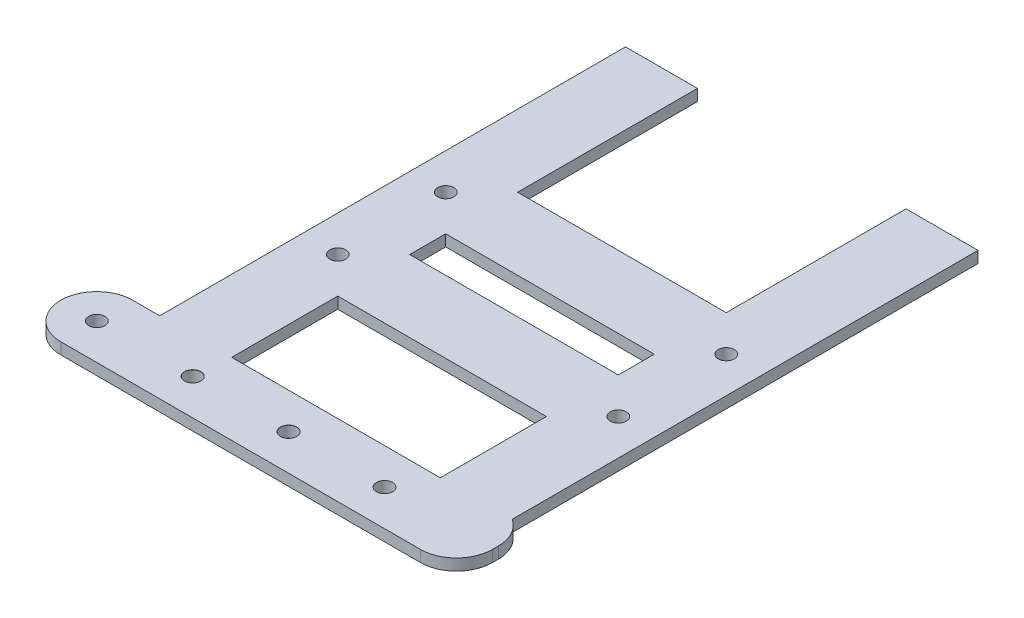
SolidWorks part; units mm, degrees
ref_plane "Front Plane" through (0, 0, 0) normal (0, 0, 1) x (1, 0, 0)
ref_plane "Top Plane" through (0, 0, 0) normal (0, 1, 0) x (1, 0, 0)
ref_plane "Right Plane" through (0, 0, 0) normal (1, 0, 0) x (0, 0, -1)
sketch "Sketch1" plane through (0, 0, 0) normal (0, 1, 0) x (1, 0, 0)
  line L1 (-50, -200) -> (50, -200)
  line L2 (-50, -200) -> (-50, 200)
  line L3 (-50, 200) -> (50, 200)
  line L4 (50, -200) -> (50, 200)
  line L5 (-50, -200) -> (50, 200) construction
  line L6 (-50, 200) -> (50, -200) construction
  point P0 (0, 0)
  dimension "D1" = 100
  dimension "D2" = 400
extrude "Boss-Extrude1" add sketch "Sketch1" along normal blind 3.175
sketch "Sketch2" plane through (0, 3.175, 0) normal (0, 1, 0) x (1, 0, 0)
  line L0 (50, 200) -> (-50, 200) construction
  line L1 (-40, 200) -> (-40, -200) construction
  line L2 (-50, -200) -> (50, -200) construction
  line L3 (-50, 95) -> (50, 95) construction
  line L4 (40, 200) -> (40, -200) construction
  line L5 (0, -200) -> (0, 200) construction
  line L6 (50, -200) -> (50, 200) construction
  line L7 (-50, 190) -> (50, 190) construction
  line L8 (-50, 200) -> (-50, -200) construction
  line L9 (-50, -190) -> (50, -190) construction
  dimension "D1" = 80
  dimension "D2" = 40
  dimension "D4" = 10
  dimension "D5" = 10
  dimension "D3" = 380
  dimension "D6" = 295
hole_wizard "M4 Clearance Hole2" positions "Sketch3" profile "Sketch5" hole size "M4" standard "AS" end condition up to next
sketch "Sketch3" plane through (0, 3.175, 0) normal (0, 1, 0) x (1, 0, 0)
  line L0 (-40, 200) -> (-40, -200) construction
  line L1 (-50, 190) -> (50, 190) construction
  line L2 (40, 200) -> (40, -200) construction
  line L3 (-50, -190) -> (50, -190) construction
  line L4 (-50, 95) -> (50, 95) construction
  point P0 (-40, 190)
  point P6 (40, 190)
  point P10 (40, -190)
  point P12 (-40, -190)
  point P17 (-40, 95)
  point P21 (40, 95)
sketch "Sketch5" plane through (-40, 3.175, -190) normal (1, 0, 0) x (0, 0, 1)
  line L0 (0, 0) -> (0, 3.175)
  line L1 (0, 3.175) -> (2.25, 3.175)
  line L2 (2.25, 3.175) -> (2.25, 0)
  line L5 (2.25, 0) -> (0, 0)
  line L11 (0, -6.35) -> (0, 107.95) construction
  dimension "Thru Hole Dia." = 4.5
  dimension "Thru Hole Depth" = 3.175
sketch "Sketch7" plane through (50, 0, 0) normal (1, 0, 0) x (0, 0, -1)
  line L1 (-200, 0) -> (200, 0)
  line L2 (-200, 0) -> (-200, 3.175)
  line L3 (-200, 3.175) -> (200, 3.175)
  line L4 (200, 0) -> (200, 3.175)
extrude "Boss-Extrude2" add sketch "Sketch7" along normal blind 20
sketch "Sketch6" plane through (0, 3.175, 0) normal (0, 1, 0) x (1, 0, 0)
  line L0 (-50, -180) -> (113.5028, -180) construction
  line L1 (-50, 200) -> (-50, -200) construction
  line L3 (-50, 180) -> (94.0039, 180) construction
  line L4 (70, 200) -> (-50, 200) construction
  line L5 (-50, -200) -> (70, -200) construction
  line L6 (16.5, 180) -> (16.5, -180) construction
  line L19 (55.5, -180) -> (55.5, 180) construction
  line L20 (-22.5, 180) -> (-22.5, -180) construction
  line L21 (-50, -170) -> (50, -170) construction
  line L22 (-22.5, -140.5) -> (55.5, -140.5) construction
  line L23 (50, 200) -> (50, -200) construction
  line L24 (70, 200) -> (-50, 200) construction
  line L25 (-50, -200) -> (70, -200) construction
  line L26 (-22.5, -110.5) -> (55.5, -110.5) construction
  line L27 (-22.5, -24.5) -> (55.5, -24.5) construction
  line L28 (-22.5, 5.5) -> (55.5, 5.5) construction
  point P4 (-22.5, -170)
  dimension "D1" = 20
  dimension "D2" = 20
  dimension "D4" = 39
  dimension "D5" = 39
  dimension "D7" = 29.5
  dimension "D8" = 100
  dimension "D3" = 33.5
  dimension "D9" = 30
  dimension "D10" = 86
  dimension "D11" = 30
hole_wizard "M4 Clearance Hole1" positions "Sketch10" profile "Sketch12" hole size "M4" standard "AS" end condition up to next
sketch "Sketch10" plane through (0, 3.175, 0) normal (0, 1, 0) x (1, 0, 0)
  point P0 (55.5, -140.5)
  point P3 (55.5, -110.5)
  point P6 (-22.5, -110.5)
  point P9 (-22.5, -140.5)
  point P12 (-22.5, -24.5)
  point P15 (-22.5, 5.5)
  point P25 (55.5, 5.5)
  point P28 (55.5, -24.5)
sketch "Sketch12" plane through (55.5, 3.175, 140.5) normal (1, 0, 0) x (0, 0, 1)
  line L0 (0, 0) -> (0, 3.175)
  line L1 (0, 3.175) -> (2.25, 3.175)
  line L2 (2.25, 3.175) -> (2.25, 0)
  line L5 (2.25, 0) -> (0, 0)
  line L11 (0, -6.35) -> (0, 107.95) construction
  dimension "Thru Hole Dia." = 4.5
  dimension "Thru Hole Depth" = 3.175
sketch "Sketch13" plane through (0, 3.175, 0) normal (0, 1, 0) x (1, 0, 0)
  line L1 (-50, -180) -> (70, -180) construction
  line L2 (-50, 200) -> (-50, -200) construction
  line L3 (70, 200) -> (70, -200) construction
  line L4 (-50, 180) -> (70, 180) construction
  line L5 (-50, 105) -> (70, 105) construction
  line L6 (-50, 85) -> (70, 85) construction
  line L7 (-32.5, -180) -> (-32.5, 85)
  line L8 (-12.5, 85) -> (-12.5, 15.5)
  line L9 (45.5, 85) -> (45.5, 15.5)
  line L10 (65.5, 85) -> (65.5, -180)
  line L11 (70, 200) -> (-50, 200) construction
  line L12 (-12.5, 85) -> (45.5, 85)
  line L13 (-12.5, -100.5) -> (45.5, -100.5)
  line L14 (-12.5, -120.5) -> (45.5, -120.5)
  line L15 (-12.5, -150.5) -> (-12.5, -180)
  line L16 (45.5, -120.5) -> (45.5, -130.5)
  line L17 (-50, 85) -> (-32.5, 85)
  line L18 (65.5, 85) -> (70, 85)
  line L19 (65.5, -180) -> (70, -180)
  line L20 (-32.5, -180) -> (-50, -180)
  line L21 (-32.5, 105) -> (-32.5, 180)
  line L22 (-12.5, 105) -> (-12.5, 180)
  line L23 (45.5, 105) -> (45.5, 180)
  line L24 (65.5, 105) -> (65.5, 180)
  line L25 (-50, 105) -> (-32.5, 105)
  line L26 (65.5, 105) -> (70, 105)
  line L27 (-50, 180) -> (-32.5, 180)
  line L28 (65.5, 180) -> (70, 180)
  line L29 (-50, 180) -> (-50, 105)
  line L30 (70, 180) -> (70, 105)
  line L31 (-50, -180) -> (-50, 85)
  line L32 (70, -180) -> (70, 85)
  line L33 (-12.5, -180) -> (45.5, -180)
  line L34 (-12.5, 180) -> (45.5, 180)
  line L35 (-12.5, 105) -> (45.5, 105)
  line L36 (-12.5, -130.5) -> (45.5, -130.5)
  line L37 (-12.5, -150.5) -> (45.5, -150.5)
  line L38 (-22.5, -140.5) -> (55.5, -140.5) construction
  line L39 (45.5, -150.5) -> (45.5, -180)
  line L40 (-12.5, -130.5) -> (-12.5, -120.5)
  line L41 (-12.5, -14.5) -> (45.5, -14.5)
  line L42 (-12.5, -34.5) -> (45.5, -34.5)
  line L43 (-12.5, 15.5) -> (45.5, 15.5)
  line L44 (-12.5, -4.5) -> (45.5, -4.5)
  line L45 (-22.5, -24.5) -> (55.5, -24.5) construction
  line L46 (-12.5, -4.5) -> (-12.5, -14.5)
  line L47 (45.5, -4.5) -> (45.5, -14.5)
  line L48 (45.5, -34.5) -> (45.5, -100.5)
  line L49 (-12.5, -34.5) -> (-12.5, -100.5)
  circle A0 centre (-40, -190) radius 2.25 construction
  circle A1 centre (-40, 190) radius 2.25 construction
  circle A2 centre (-40, 95) radius 2.25 construction
  circle A3 centre (-22.5, -140.5) radius 2.25 construction
  circle A4 centre (55.5, -140.5) radius 2.25 construction
  dimension "D4" = 10
  dimension "D5" = 10
  dimension "D1" = 10
  dimension "D2" = 10
  dimension "D3" = 10
  dimension "D6" = 10
  dimension "D7" = 10
  dimension "D9" = 95
  dimension "D10" = 10
  dimension "D11" = 10
  dimension "D12" = 10
  dimension "D13" = 10
  dimension "D14" = 10
  dimension "D15" = 10
  dimension "D16" = 10
  dimension "D17" = 10
extrude "Cut-Extrude1" cut sketch "Sketch13" against normal up to surface (3.175 mm away) up to face at (55.5, 0, 138.25)
fillet "Fillet1" radius 10 12 edges at (70, 1.5875, -180) (70, 1.5875, -200) (-50, 1.5875, -200) (-50, 1.5875, -180) (-50, 1.5875, -85) (-50, 1.5875, -105) (70, 1.5875, -105) (70, 1.5875, -85) (70, 1.5875, 180) (-50, 1.5875, 180) (70, 1.5875, 200) (-50, 1.5875, 200)
ref_plane "Plane1" through (0, 0, 67.5) normal (0, 0, 1) x (1, 0, 0)
ref_plane "Plane2" through (0, 0, 180) normal (0, 0, -1) x (-1, 0, 0)
sketch "Sketch14" plane through (0, 3.175, 0) normal (0, 1, 0) x (1, 0, 0)
  line L0 (-12.5, -100.5) -> (45.5, -100.5) construction
  line L1 (70, -100.5) -> (-50, -100.5) construction
  line L2 (70, -50.5) -> (70, 200)
  line L3 (70, 200) -> (-50, 200)
  line L4 (-50, -50.5) -> (-50, 200)
  line L7 (60, 200) -> (-40, 200) construction
  line L8 (70, 96.6484) -> (70, 93.3516) construction
  line L9 (-50, -50.5) -> (70, -50.5)
  line L10 (-50, -100.5) -> (-50, -50.5) construction
  line L11 (70, -100.5) -> (70, -50.5) construction
  dimension "D1" = 50
extrude "Cut-Extrude2" cut sketch "Sketch14" against normal up to surface (3.175 mm away) up to face at (16.5, 0, 165.25)
hole_wizard "M4 Clearance Hole3" positions "Sketch15" profile "Sketch16" hole size "M4" standard "ANSI Metric" end condition up to next
sketch "Sketch15" plane through (0, 0, 0) normal (0, -1, 0) x (-1, 0, 0)
  line L0 (-40, -190) -> (40, -190)
  point P0 (-13.3333, -190)
  point P2 (13.3333, -190)
  dimension "D1" = 26.6667
  dimension "D2" = 26.6667
sketch "Sketch16" plane through (13.3333, 0, 190) normal (1, 0, 0) x (0, 0, -1)
  line L0 (0, 0) -> (0, 3.175)
  line L1 (0, 3.175) -> (2.275, 3.175)
  line L2 (2.25, 3.15) -> (2.25, 0.025)
  line L3 (2.25, 0.025) -> (2.275, 0)
  line L5 (2.275, 0) -> (0, 0)
  line L6 (-2.25, 0.025) -> (-2.275, 0) construction
  line L7 (2.275, 3.175) -> (2.25, 3.15)
  line L8 (-2.275, 3.175) -> (-2.25, 3.15) construction
  line L11 (0, -6.35) -> (0, 107.95) construction
  dimension "Thru Hole Dia." = 4.5
  dimension "Thru Hole Depth" = 3.175
  dimension "Near C'Sink Dia." = 4.55
  dimension "Near C'Sink Angle" = 90
  dimension "Far C'Sink Dia." = 4.55
  dimension "Far C'Sink Angle" = 90
equation "\"D2@Sketch6\"=\"D1@Sketch6\""
equation "\"D2@Sketch2\"=\"D1@Sketch2\"/2"
equation "\"D11@Sketch13\"=\"D10@Sketch13\""
equation "\"D13@Sketch13\"=\"D10@Sketch13\""
equation "\"D12@Sketch13\"=\"D10@Sketch13\""
equation "\"D15@Sketch13\"=\"D14@Sketch13\""
equation "\"D16@Sketch13\"=\"D14@Sketch13\""
equation "\"D17@Sketch13\"=\"D14@Sketch13\""
